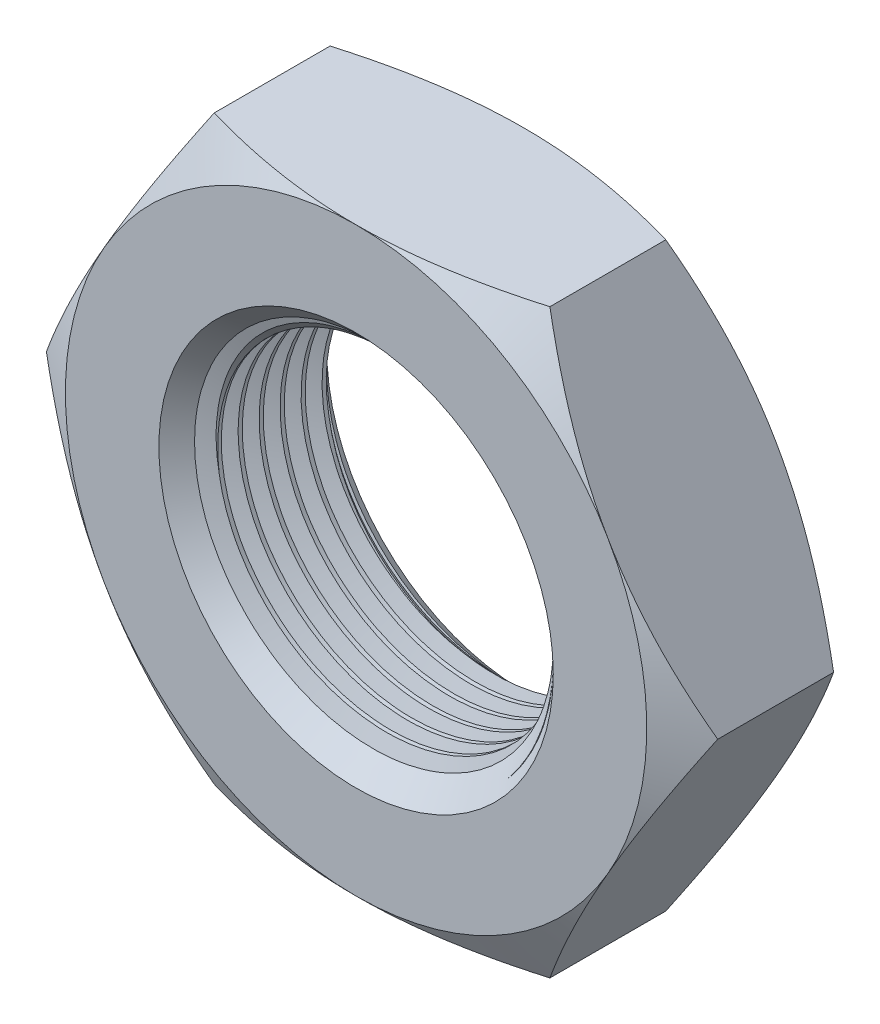
SolidWorks part; units mm, degrees
ref_plane "Спереди" through (0, 0, 0) normal (0, 0, 1) x (1, 0, 0)
ref_plane "Сверху" through (0, 0, 0) normal (0, 1, 0) x (1, 0, 0)
ref_plane "Справа" through (0, 0, 0) normal (1, 0, 0) x (0, 0, -1)
sketch "Эскиз16" plane through (0, 0, 0) normal (0, 0, 1) x (1, 0, 0)
  line L6 (0, -2.5) -> (50000, -2.5) construction
  line L8 (4, 0) -> (2, 3.4641)
  line L9 (2, 3.4641) -> (-2, 3.4641)
  line L10 (-2, 3.4641) -> (-4, 0)
  line L11 (-4, 0) -> (-2, -3.4641)
  line L12 (-2, -3.4641) -> (2, -3.4641)
  line L13 (2, -3.4641) -> (4, 0)
  circle A1 centre (0, 0) radius 3.4641 construction
extrude "Бобышка-Вытянуть4" add sketch "Эскиз16" along normal blind 2
sketch "Эскиз17" plane through (0, 0, 0) normal (0, 0, -1) x (-1, 0, 0)
  circle A0 centre (0, 0) radius 3.4641
extrude "Вырез-Вытянуть1" cut sketch "Эскиз17" against normal blind 2 draft 60 flip side to cut
sketch "Эскиз18" plane through (0, 0, 2) normal (0, 0, 1) x (1, 0, 0)
  circle A0 centre (0, 0) radius 3.4641
extrude "Вырез-Вытянуть2" cut sketch "Эскиз18" against normal blind 2 draft 60 flip side to cut
sketch "Эскиз19" plane through (0, 0, 2) normal (0, 0, 1) x (1, 0, 0)
  circle A0 centre (0, 0) radius 2
extrude "Вырез-Вытянуть3" cut sketch "Эскиз19" against normal blind 2
chamfer "Фаска1" distance 0.35 angle 45 1 edges at (2, 0, 2)
chamfer "Фаска2" distance 0.35 angle 45 1 edges at (2, 0, 0)
sketch "Эскиз21" plane through (0, 0, 0) normal (0, 1, 0) x (1, 0, 0)
  line L0 (-1.7275, -0.2415) -> (-1.7258, 0.1868)
  line L2 (-1.7275, -0.2415) -> (-2.2408, 0.0144)
  line L3 (-2.2408, 0.0144) -> (-1.7258, 0.1868)
  arc A0 (-1.7269, -0.0215) -> (-1.7266, -0.0121) centre (-1.8692, -0.0116) ccw
  dimension "D1" = 0.4283
  dimension "D2" = 0.515
sketch "Эскиз22" plane through (0, 0, 0) normal (0, 0, 1) x (1, 0, 0)
  circle A0 centre (0, 0) radius 2.2408
  point P3 (-2.2408, 0)
curve "Спираль1" pitch 0.25 height 2.3125 radius 2.2408 left hand yes centre (0, 0, 0) axis (0, 0, 1) start towards (-1, 0, 0)
sketch "Эскиз23" plane through (-3, 1.7321, 0) normal (-0.866, 0.5, 0) x (0, 0, 1)
sweep "Вырез-По траектории19" cut profiles "Эскиз21" path "Спираль1"
